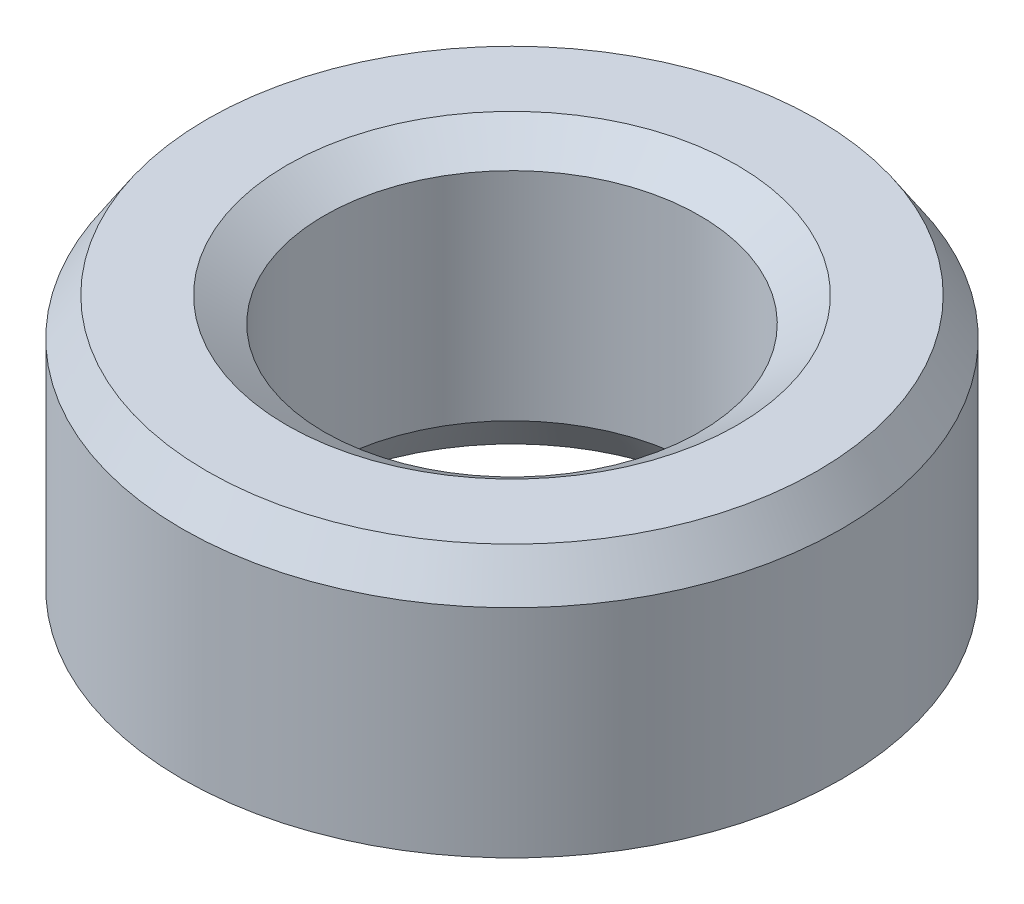
SolidWorks part; units mm, degrees
ref_plane "Front Plane" through (0, 0, 0) normal (0, 0, 1) x (1, 0, 0)
ref_plane "Top Plane" through (0, 0, 0) normal (0, 1, 0) x (1, 0, 0)
ref_plane "Right Plane" through (0, 0, 0) normal (1, 0, 0) x (0, 0, -1)
sketch "Sketch1" plane through (0, 0, 0) normal (0, 1, 0) x (1, 0, 0)
  circle A0 centre (0, 0) radius 22.5
  dimension "SLEEVE_OD" = 45
extrude "Boss-Extrude1" add sketch "Sketch1" along normal blind 19.0382
sketch "Sketch2" plane through (0, 0, 0) normal (0, 1, 0) x (1, 0, 0)
  circle A0 centre (0, 0) radius 12.8026
  dimension "BORE_D" = 25.6051
extrude "Cut-Extrude1" cut sketch "Sketch2" along normal through all
chamfer "Chamfer1" distance 2.5644 angle 33.389 4 edges at (0, 19.0382, 12.8026) (0, 0, 12.8026) (0, 0, 22.5) (0, 19.0382, 22.5) first distance on face at (0, 19.0382, 12.8026) first distance on face at (0, 0, 12.8026) first distance on face at (0, 19.0382, 22.5)
